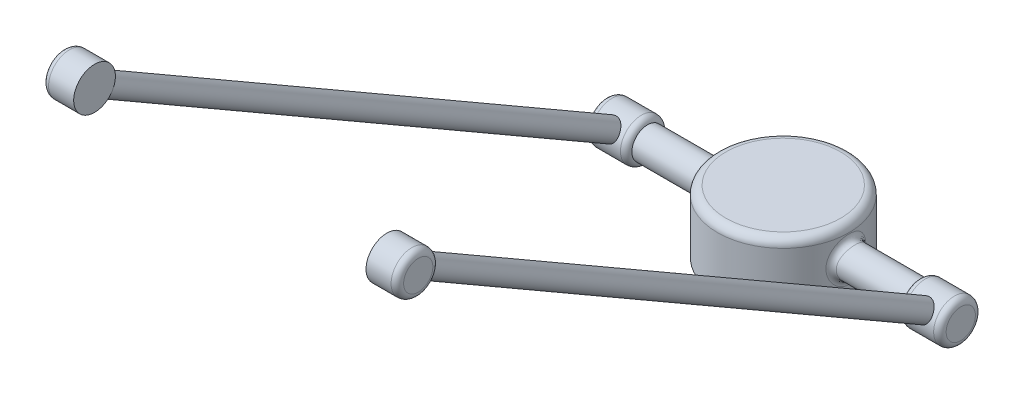
SolidWorks part; units mm, degrees
material "Polyester Resin"
ref_plane "Front Plane" through (0, 0, 0) normal (0, 0, 1) x (1, 0, 0)
ref_plane "Top Plane" through (0, 0, 0) normal (0, 1, 0) x (1, 0, 0)
ref_plane "Right Plane" through (0, 0, 0) normal (1, 0, 0) x (0, 0, -1)
sketch "Sketch1" plane through (0, 0, 0) normal (0, 1, 0) x (1, 0, 0)
  circle A0 centre (0, 0) radius 31.5
  dimension "D1" = 63
extrude "Boss-Extrude1" add sketch "Sketch1" along normal blind 30
sketch "Sketch2" plane through (0, 0, 0) normal (1, 0, 0) x (0, 0, -1)
  line L0 (0, 0) -> (0, 30) construction
  line L1 (31.5, 30) -> (-31.5, 30) construction
  circle A0 centre (0, 15) radius 7.5
  dimension "D1" = 15
extrude "Boss-Extrude2" add sketch "Sketch2" along normal blind 65
sketch "Sketch3" plane through (65, 0, 0) normal (1, 0, 0) x (0, 0, -1)
  circle A0 centre (0, 15) radius 10
  dimension "D1" = 20
extrude "Boss-Extrude3" add sketch "Sketch3" along normal blind 20
ref_axis "Axis1" through (0, 15, 0) along (1, 0, 0)
ref_plane "Plane1" through (0, 3.75, 6.4952) normal (0, -0.5, -0.866) x (1, 0, 0)
sketch "Sketch4" plane through (0, 3.75, 6.4952) normal (0, -0.5, -0.866) x (1, 0, 0)
  line L0 (0, -12.9904) -> (65, -12.9904) construction
  line L2 (65, -2.9904) -> (65, -22.9904) construction
  circle A0 centre (75, -12.9904) radius 5
  dimension "D1" = 10
  dimension "D2" = 10
extrude "Boss-Extrude4" add sketch "Sketch4" against normal blind 300
sketch "Sketch5" plane through (85, 0, 0) normal (1, 0, 0) x (0, 0, -1)
  line L0 (-259.8076, 165) -> (0, 15) construction
  line L1 (-257.3076, 169.3301) -> (-262.3076, 160.6699) construction
  circle A0 centre (-259.8076, 165) radius 10
  dimension "D1" = 20
extrude "Boss-Extrude5" add sketch "Sketch5" against normal blind 15
fillet "Fillet1" radius 3 4 edges at (30.6305, 16.492, -7.3501) (65, 15, -10) (85, 15, -10) (85, 165, 249.8076)
mirror "Mirror1" about plane through (0, 0, 0) normal (1, 0, 0) of "Boss-Extrude5", "Boss-Extrude2", "Fillet1", "Boss-Extrude4", "Boss-Extrude3"
fillet "Fillet2" radius 4 1 edges at (0, 30, 31.5)
sketch "Sketch7" plane through (0, 0, 0) normal (0, 0, 1) x (1, 0, 0)
  line L0 (0, 0) -> (0, 10) construction
  line L2 (-12.5, 10) -> (12.5, 10) construction
  circle A1 centre (-12.5, 10) radius 4
  circle A2 centre (12.5, 10) radius 4
  point P6 (0, 10)
  dimension "D1" = 25
  dimension "D2" = 8
  dimension "D3" = 8
  dimension "D4" = 10
extrude "Boss-Extrude6" [suppressed] add sketch "Sketch7" along normal blind 80
sketch "Sketch8" [suppressed] plane through (0, 0, 80) normal (0, 0, 1) x (1, 0, 0)
  line L0 (-12.5, 10) -> (12.5, 10) construction
  line L1 (-20, 20) -> (20, 20)
  line L6 (-20, 20) -> (-20, -40)
  line L7 (-20, -40) -> (20, -40)
  line L8 (20, 20) -> (20, -40)
  line L9 (-20, 20) -> (20, -40) construction
  line L10 (-20, -40) -> (20, 20) construction
  line L11 (0, 20) -> (0, 10) construction
  line L12 (0, 20) -> (0, -3) construction
  circle A4 centre (0, -3) radius 2.555
  point P0 (0, -10)
  dimension "D5" = 23
  dimension "D4" = 5.11
  dimension "D1" = 10
  dimension "D2" = 60
  dimension "D3" = 40
extrude "Boss-Extrude7" [suppressed] add sketch "Sketch8" along normal blind 4
sketch "Sketch10" [suppressed] plane through (0, 20, 0) normal (0, 1, 0) x (1, 0, 0)
  line L0 (-20, -84) -> (-20, -80) construction
  line L1 (20, -80) -> (-20, -80)
  line L2 (20, -80) -> (20, -93)
  line L3 (20, -93) -> (-20, -93)
  line L4 (-20, -80) -> (-20, -93)
  dimension "D1" = 13
extrude "Boss-Extrude8" [suppressed] add sketch "Sketch10" along normal blind 3
sketch "Sketch11" [suppressed] plane through (0, -40, 0) normal (0, -1, 0) x (1, 0, 0)
  line L0 (-20, 84) -> (-20, 80) construction
  line L1 (20, 80) -> (-20, 80)
  line L2 (20, 80) -> (20, 93)
  line L3 (20, 93) -> (-20, 93)
  line L4 (-20, 80) -> (-20, 93)
  dimension "D1" = 13
extrude "Boss-Extrude9" [suppressed] add sketch "Sketch11" along normal blind 3
fillet "Fillet3" [suppressed] radius 5
fillet "Fillet4" [suppressed] radius 2
sketch "Sketch6" plane through (0, 0, 0) normal (0, -1, 0) x (1, 0, 0)
  circle A0 centre (0, 0) radius 29
  dimension "D1" = 58
extrude "Cut-Extrude1" cut sketch "Sketch6" against normal offset from surface (25 mm away) 5 up to face at (0, 30, 27.5)
chamfer "Chamfer1" distance 15 angle 45 1 edges at (0, 25, 29)
